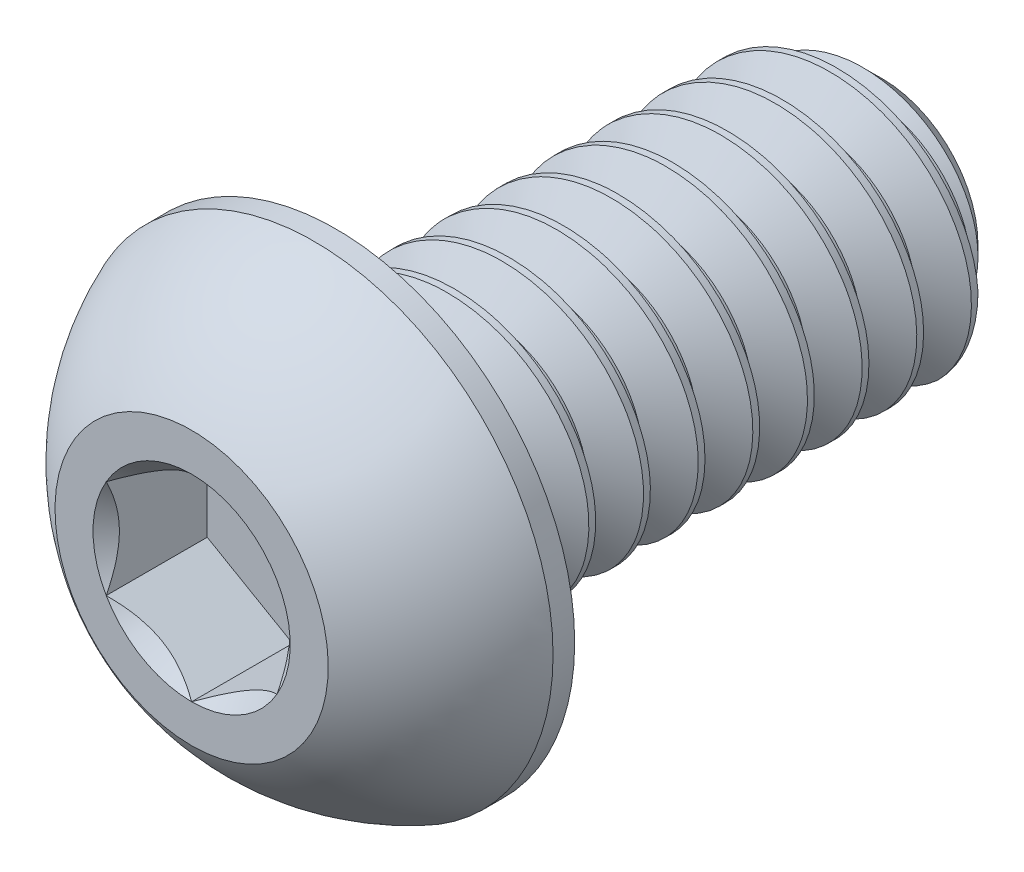
SolidWorks part; units mm, degrees
ref_plane "Front" through (0, 0, 0) normal (0, 0, 1) x (1, 0, 0)
ref_plane "Top" through (0, 0, 0) normal (0, 1, 0) x (1, 0, 0)
ref_plane "Right" through (0, 0, 0) normal (1, 0, 0) x (0, 0, -1)
sketch "Sketch1" plane through (0, 0, 0) normal (1, 0, 0) x (0, 0, -1)
  line L2 (3.3528, 3.175) -> (16.0528, 3.175)
  line L3 (16.0528, 3.175) -> (16.0528, 0)
  line L4 (16.0528, 0) -> (3.3528, 0)
  line L6 (2.8499, 5.5499) -> (3.3528, 5.5499) construction
  line L7 (16.0528, 3.175) -> (16.0528, -3.175) construction
  line L8 (0, 0) -> (3.3528, 0) construction
  line L9 (3.3528, 5.5499) -> (3.3528, -5.5499) construction
  line L11 (3.3528, 3.175) -> (3.3528, 0)
  line L13 (0, 1.9844) -> (0, -1.9844) construction
  line L14 (0, 1.9844) -> (0, 3.175) construction
  arc A3 (0, 3.175) -> (2.8499, 5.5499) centre (5.0603, 0) cw construction
  dimension "D1" = 0.5029
revolve "Revolve1" add sketch "Sketch1" angle 360 mid plane about L4
sketch "Sketch3" plane through (0, 0, -16.0528) normal (0, 0, -1) x (-1, 0, 0)
  circle A0 centre (0, 0) radius 3.175
curve "Helix/Spiral1" pitch 1.27 height 13.97 radius 3.175 centre (0, 0, -16.0528) axis (0, 0, 1) start towards (0, 1, 0)
sketch "Sketch2" plane through (0, 0, 0) normal (1, 0, 0) x (0, 0, -1)
  line L0 (16.0528, 3.175) -> (17.164, 3.175)
  line L1 (17.164, 3.175) -> (16.6878, 2.3501)
  line L2 (16.6878, 2.3501) -> (16.529, 2.3501)
  line L3 (16.529, 2.3501) -> (16.0528, 3.175)
  line L4 (16.2909, 2.7626) -> (16.9259, 2.7626) construction
  dimension "D1" = 60
  dimension "D2" = 0.1588
  dimension "D3" = 0.635
chamfer "Chamfer1" distance 0.9525 angle 45 1 edges at (0, 3.175, -16.0528)
sweep "Cut-Sweep1" cut profiles "Sketch2" path "Helix/Spiral1" align with end faces yes
sketch "Sketch7" plane through (0, 0, 0) normal (1, 0, 0) x (0, 0, -1)
  line L6 (2.8499, 5.5499) -> (3.3528, 5.5499) construction
  line L8 (0, 0) -> (3.3528, 0) construction
  line L11 (3.3528, 5.5499) -> (3.3528, -5.5499) construction
  line L12 (2.8499, 5.5499) -> (3.3528, 5.5499)
  line L13 (0, 0) -> (3.3528, 0)
  line L14 (0, 1.9844) -> (0, -1.9844) construction
  line L15 (3.3528, 5.5499) -> (3.3528, 0)
  line L16 (0, 3.175) -> (0, 0)
  arc A2 (2.8499, 5.5499) -> (0, 3.175) centre (5.0603, 0) ccw construction
  arc A3 (2.8499, 5.5499) -> (0, 3.175) centre (5.0603, 0) ccw
revolve "Revolve2" add sketch "Sketch7" angle 360 mid plane about L13
sketch "Sketch5" plane through (0, 0, 0) normal (0, 0, 1) x (1, 0, 0)
  line L1 (1.9844, -1.1457) -> (1.9844, 1.1457)
  line L2 (1.9844, 1.1457) -> (0, 2.2914)
  line L3 (0, 2.2914) -> (-1.9844, 1.1457)
  line L4 (-1.9844, 1.1457) -> (-1.9844, -1.1457)
  line L5 (-1.9844, -1.1457) -> (0, -2.2914)
  line L6 (0, -2.2914) -> (1.9844, -1.1457)
  circle A0 centre (0, 0) radius 1.9844 construction
extrude "Cut-Extrude2" cut sketch "Sketch5" against normal blind 2.347
sketch "Sketch6" plane through (0, 0, 0) normal (0, 0, 1) x (1, 0, 0)
  circle A0 centre (0, 0) radius 2.2914
extrude "Cut-Extrude3" cut sketch "Sketch6" against normal blind 2.347 draft 45
sketch "Sketch9" [suppressed] plane through (0, 0, -3.3528) normal (0, 0, 1) x (1, 0, 0)
  circle A2 centre (0, 0) radius 3.175
extrude "Boss-Extrude2" [suppressed] add sketch "Sketch9" against normal offset from surface (25.4 mm away) 22.225 up to face at (0, 2.2225, -16.0528)
sketch "Sketch10" plane through (0, 0, 0) normal (1, 0, 0) x (0, 0, -1)
  line L0 (16.0528, 3.175) -> (16.0528, -3.175) construction
  point P0 (14.1478, -3.175)
  dimension "D1" = 1.905
equation "\"D3@Helix/Spiral1\" = \"Lg@Sketch1\" + \"D4@Helix/Spiral1\""
equation "\"D2@Sketch2\" = \"D4@Helix/Spiral1\" * .125"
equation "\"D3@Sketch2\" = \"D4@Helix/Spiral1\" * .5"
equation "\"D1@Chamfer1\" = \"D4@Helix/Spiral1\" * .75"
equation "\"D1@Cut-Extrude2\" = \"Head Ht@Sketch1\" * .7"
equation "\"D1@Sketch1\" = \"Head Ht@Sketch1\" * .15"
equation "\"D1@Sketch10\" = \"D4@Helix/Spiral1\" * 1.5"
equation "\"D1@Cut-Extrude3\" = \"D1@Cut-Extrude2\""
